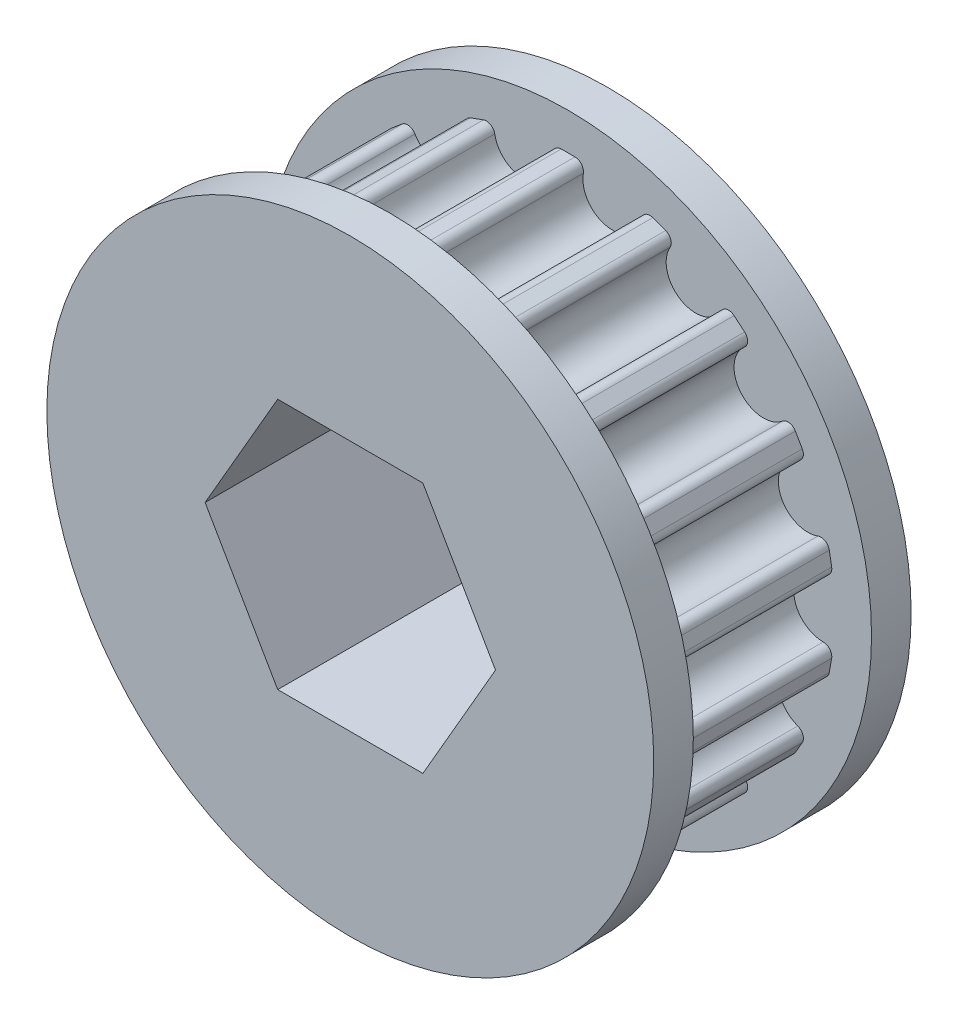
SolidWorks part; units mm, degrees
material "PE High Density"
ref_plane "Front Plane" through (0, 0, 0) normal (0, 0, 1) x (1, 0, 0)
ref_plane "Top Plane" through (0, 0, 0) normal (0, 1, 0) x (1, 0, 0)
ref_plane "Right Plane" through (0, 0, 0) normal (1, 0, 0) x (0, 0, -1)
sketch "Sketch2" plane through (0, 0, 0) normal (0, 0, 1) x (1, 0, 0)
  circle A0 centre (0, 0) radius 14.3239
  dimension "D1" = 28.6479
extrude "PD" add sketch "Sketch2" along normal mid plane 9
sketch "Sketch3" plane through (0, 0, 4.5) normal (0, 0, 1) x (1, 0, 0)
  line L0 (0, 0) -> (0, 13.4539) construction
  line L1 (0, 0) -> (2.2373, 12.6882) construction
  line L2 (0, 13.4539) -> (0.3469, 13.4539)
  line L3 (0, 13.4539) -> (0, 14.3239)
  line L4 (4.6015, 12.6426) -> (4.8991, 13.4601)
  line L5 (4.6015, 12.6426) -> (4.2756, 12.7612)
  line L6 (2.2373, 12.6882) -> (2.4873, 14.1063) construction
  arc A0 (0.3469, 13.4539) -> (0.7702, 12.9488) centre (0.3469, 13.0239) cw
  arc A1 (0.7702, 12.9488) -> (3.705, 12.4313) centre (2.2373, 12.6882) ccw
  circle A2 centre (0, 0) radius 14.3239 construction
  arc A3 (0, 14.3239) -> (4.8991, 13.4601) centre (0, 0) cw
  arc A4 (4.2756, 12.7612) -> (3.705, 12.4313) centre (4.1285, 12.3571) ccw
  point P8 (1.9785, 11.2208)
  dimension "D1" = 0.43
  dimension "D2" = 1.49
  dimension "D3" = 0.87
  dimension "D4" = 10
  dimension "D5" = 2.93
extrude "Teeth" cut sketch "Sketch3" against normal up to surface (9 mm away) up to face at (14.3239, 0, -4.5)
pattern_circular "CirPattern1" count 18 over 360 about axis through (0, 0, 4.5) along (0, 0, 1) of "Teeth"
sketch "Sketch4" plane through (0, 0, 4.5) normal (0, 0, 1) x (1, 0, 0)
  circle A0 centre (0, 0) radius 15.3239
  dimension "D1" = 30.6479
extrude "Flange" add sketch "Sketch4" along normal blind 2
mirror "Flange 2" about plane through (0, 0, 0) normal (0, 0, 1) of "Flange"
sketch "Sketch6" plane through (0, 0, 0) normal (0, 0, 1) x (1, 0, 0)
  line L1 (7.3323, 0) -> (3.6662, 6.35)
  line L2 (3.6662, 6.35) -> (-3.6662, 6.35)
  line L3 (-3.6662, 6.35) -> (-7.3323, 0)
  line L4 (-7.3323, 0) -> (-3.6662, -6.35)
  line L5 (-3.6662, -6.35) -> (3.6662, -6.35)
  line L6 (3.6662, -6.35) -> (7.3323, 0)
  circle A0 centre (0, 0) radius 6.35 construction
  dimension "D1" = 12.7
extrude "Cut-Extrude2" cut sketch "Sketch6" against normal through all both and the other way through all
sketch "Sketch7" [suppressed] plane through (0, 0, -6.9) normal (0, 0, -1) x (-1, 0, 0)
  line L0 (3.6662, 6.35) -> (7.3323, 0) construction
  line L1 (7.3323, 0) -> (3.6662, -6.35) construction
  line L2 (3.6662, -6.35) -> (-3.6662, -6.35) construction
  line L3 (-3.6662, -6.35) -> (-7.3323, 0) construction
  line L4 (-7.3323, 0) -> (-3.6662, 6.35) construction
  line L5 (-3.6662, 6.35) -> (3.6662, 6.35) construction
  line L6 (3.6662, 6.35) -> (7.3323, 0)
  line L7 (7.3323, 0) -> (3.6662, -6.35)
  line L8 (3.6662, -6.35) -> (-3.6662, -6.35)
  line L9 (-3.6662, -6.35) -> (-7.3323, 0)
  line L10 (-7.3323, 0) -> (-3.6662, 6.35)
  line L11 (-3.6662, 6.35) -> (3.6662, 6.35)
  circle A0 centre (0, 0) radius 4
  circle A1 centre (0, 0) radius 10.5493
  circle A2 centre (0, 0) radius 10.5493
  line M2 (3.6662, 6.35) -> (7.3323, 0)
  line M3 (7.3323, 0) -> (3.6662, -6.35)
  line M4 (3.6662, -6.35) -> (-3.6662, -6.35)
  line M5 (-3.6662, -6.35) -> (-7.3323, 0)
  line M6 (-7.3323, 0) -> (-3.6662, 6.35)
  line M7 (-3.6662, 6.35) -> (3.6662, 6.35)
  dimension "D1" = 0
extrude "Boss-Extrude1" [suppressed] add sketch "Sketch7" against normal blind 13.8 contours A0 M2 M7 M6 M5 M4 M3
equation "\"D1@Sketch4\"= 16 + 2"
equation "\"D1@CirPattern1\" = 16"
equation "\"D4@Sketch3\" = 180 / 16"
equation "\"D1@Sketch2\" = 16 * 5 / pi"
